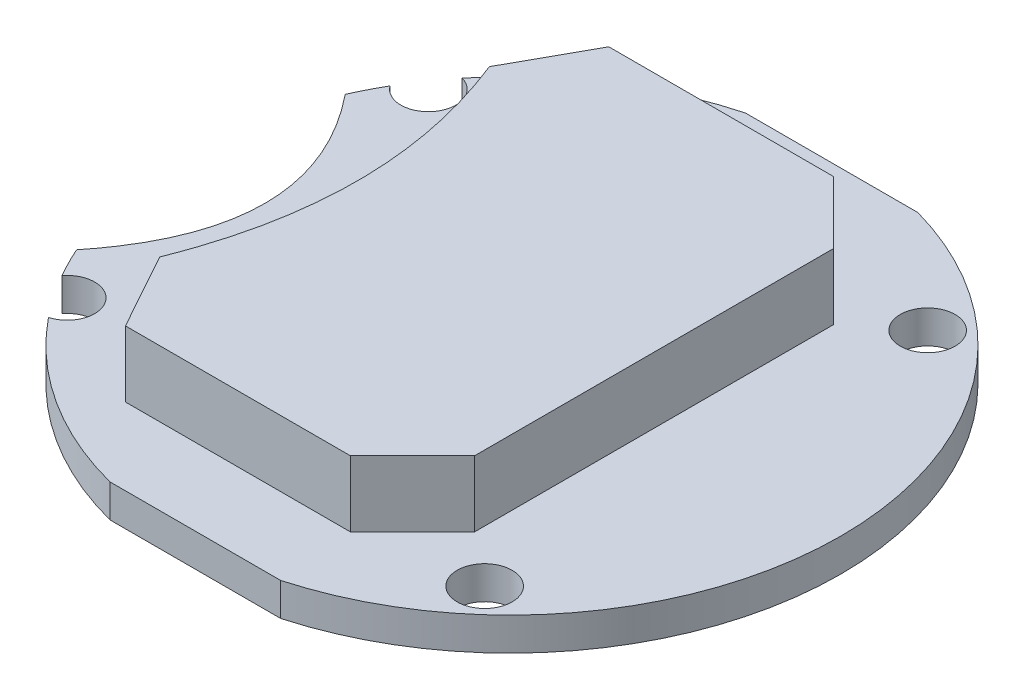
SolidWorks part; units mm, degrees
ref_plane "Спереди" through (0, 0, 0) normal (0, 0, 1) x (1, 0, 0)
ref_plane "Сверху" through (0, 0, 0) normal (0, 1, 0) x (1, 0, 0)
ref_plane "Справа" through (0, 0, 0) normal (1, 0, 0) x (0, 0, -1)
sketch "Эскиз1" plane through (0, 0, 0) normal (0, 1, 0) x (1, 0, 0)
  line L0 (-5, 14.5) -> (5, 14.5)
  line L1 (0, 15.6135) -> (0, -10.4601) construction
  line L2 (-31.7501, 0) -> (41.8405, 0) construction
  line L3 (-5, -14.5) -> (5, -14.5)
  line L4 (5, 9.6718) -> (5, -24.8067) construction
  line L5 (-5, 9.6718) -> (-5, -24.8067) construction
  line L6 (-13, 18.824) -> (-13, -24.3564)
  line L7 (-13, 6.5) -> (-7.4414, 0) construction
  line L8 (-7.4414, 0) -> (-13, -6.5) construction
  line L9 (-13, -6.5) -> (-13.5225, -7.5821) construction
  line L10 (-13.5225, -7.5821) -> (-13, -9.0189) construction
  line L11 (-13, 6.5) -> (-13.5225, 7.5821) construction
  line L12 (-13.5225, 7.5821) -> (-13, 9.0189) construction
  arc A0 (5, 14.5) -> (5, -14.5) centre (0.9404, 0) cw
  arc A3 (-5, 14.5) -> (-13, 9.0189) centre (-0.9367, -0.0094) ccw
  arc A4 (-5, -14.5) -> (-13, -9.0189) centre (-0.9367, 0.0094) cw
  spline S0 degree 2 poles (-13, 6.5) (-7.4414, 0) (-13, -6.5) knots 0 0 0 1 1 1
  spline S1 degree 2 poles (-13, -6.5) (-13.5225, -7.5821) (-13, -9.0189) knots 0 0 0 1 1 1
  spline S2 degree 2 poles (-13, 6.5) (-13.5225, 7.5821) (-13, 9.0189) knots 0 0 0 1 1 1
  point P7 (0, 14.5)
  point P11 (16, 0)
  point P13 (16, 0)
  point P17 (-16, 0)
  dimension "D1" = 10
  dimension "D2" = 29
  dimension "D3" = 11
  dimension "D4" = 11
  dimension "D5" = 8
  dimension "D6" = 6.5
  dimension "D7" = 6.5
extrude "Бобышка-Вытянуть1" add sketch "Эскиз1" along normal blind 1.5 contours L6 S0 A4 L3 A0 L0 A3 region at (1.1567, 0, 0)
sketch "Эскиз3" plane through (0, 1.5, 0) normal (0, 1, 0) x (1, 0, 0)
  line L0 (4.669, -11) -> (7.4974, -8.1716)
  line L5 (-7.5026, -11) -> (7.501, 10.9976) construction
  line L6 (-7.4968, 11.0015) -> (7.4974, -11.0024) construction
  line L7 (-16.9863, 0) -> (25.6975, 0) construction
  line L8 (4.669, 11) -> (7.4974, 8.1716)
  line L10 (7.4974, 8.1716) -> (7.4974, -8.1716)
  line L12 (-7.5026, -7.5) -> (-5.5661, -11)
  line L13 (-7.5026, 7.5) -> (-5.5661, 11)
  line L14 (-5.5661, 11) -> (4.669, 11)
  line L15 (-5.5661, -11) -> (4.669, -11)
  line L17 (-7.5026, 7.5) -> (-4.5026, 0) construction
  line L18 (-4.5026, 0) -> (-7.5026, -7.5) construction
  spline S0 degree 2 poles (-7.5026, 7.5) (-4.5026, 0) (-7.5026, -7.5) knots 0 0 0 1 1 1
  point P0 (0, 0)
  point P12 (-7.5026, -7.5)
  point P17 (-6.0026, 0)
  dimension "D1" = 22
  dimension "D2" = 15
  dimension "D3" = 3.5
  dimension "D4" = 4
  dimension "D5" = 4
extrude "Бобышка-Вытянуть2" add sketch "Эскиз3" along normal blind 3
sketch "Эскиз5" plane through (0, 1.5, 0) normal (0, 1, 0) x (1, 0, 0)
  line L0 (-18.9148, 0) -> (21.4157, 0) construction
  circle A0 centre (9.8631, 10.081) radius 1.25
  circle A1 centre (-10.9978, 8.2188) radius 1.25
  circle A2 centre (9.8631, -10.081) radius 1.25
  circle A3 centre (-10.9978, -8.2188) radius 1.25
  point P7 (0, 0)
  point P12 (0, 0)
  dimension "D1" = 2.5
extrude "Вырез-Вытянуть2" cut sketch "Эскиз5" against normal through all
sketch "Эскиз7" plane through (0, 1.5, 0) normal (0, 1, 0) x (1, 0, 0)
  line L0 (-13, 9.0189) -> (-13, 6.5) construction
  line L1 (-13, -6.5) -> (-13, -9.0189) construction
  line L2 (-13, 9.0189) -> (-13, 6.5)
  line L3 (-13, -6.5) -> (-13, -9.0189)
  line L6 (-13, 6.5) -> (-12.7156, 6.0776)
  line L7 (-5, 14.5) -> (-2.8426, 14.5)
  line L8 (-2.7639, -14.5) -> (-5, -14.5)
  line L9 (-13, -6.5) -> (-12.6955, -6.0737)
  arc A1 (5, -14.5) -> (5, 14.5) centre (0.9404, 0) ccw construction
  arc A2 (-5, 14.5) -> (-13, 9.0189) centre (-0.9367, -0.0094) ccw construction
  arc A3 (-5, 14.5) -> (-13, 9.0189) centre (-0.9367, -0.0094) ccw
  arc A4 (-13, -9.0189) -> (-5, -14.5) centre (-0.9367, 0.0094) ccw construction
  arc A5 (-13, -9.0189) -> (-5, -14.5) centre (-0.9367, 0.0094) ccw
  arc A6 (-2.8426, 14.5) -> (-12.7156, 6.0776) centre (0.998, 0) ccw
  arc A7 (-12.6955, -6.0737) -> (-2.7639, -14.5) centre (0.998, 0) ccw
  point P1 (0, 0)
  point P3 (15.998, 0)
  point P4 (15.998, 0)
  point P15 (-2.8426, 14.5)
  point P17 (-12.7156, 6.0776)
  point P19 (-2.7639, -14.5)
  point P24 (-12.6955, -6.0737)
extrude "Вырез-Вытянуть3" cut sketch "Эскиз7" against normal through all
